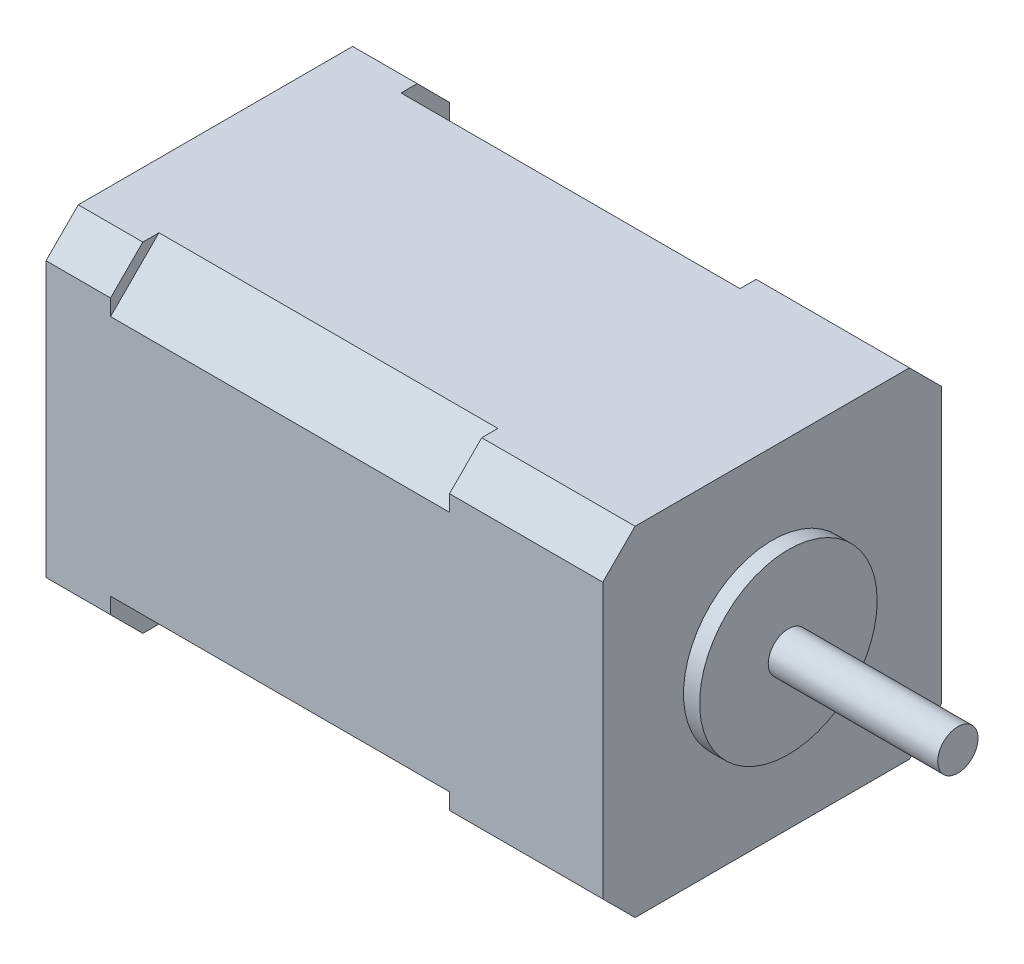
SolidWorks part; units mm, degrees
ref_plane "前视基准面" through (0, 0, 0) normal (0, 0, 1) x (1, 0, 0)
ref_plane "上视基准面" through (0, 0, 0) normal (0, 1, 0) x (1, 0, 0)
ref_plane "右视基准面" through (0, 0, 0) normal (1, 0, 0) x (0, 0, -1)
other "Configuration Table"
sketch "草图1" plane through (0, 0, 0) normal (1, 0, 0) x (0, 0, -1)
  line L1 (-21, 21) -> (21, 21)
  line L2 (-21, 21) -> (-21, -21)
  line L3 (-21, -21) -> (21, -21)
  line L4 (21, 21) -> (21, -21)
  dimension "D1" = 42
  dimension "D2" = 42
  dimension "D3" = 21
  dimension "D4" = 21
extrude "凸台-拉伸1" add sketch "草图1" along normal blind 69
sketch "草图2" plane through (69, 0, 0) normal (1, 0, 0) x (0, 0, -1)
  circle A0 centre (0, 0) radius 11
  dimension "D1" = 22
extrude "凸台-拉伸2" add sketch "草图2" along normal blind 2
sketch "草图3" plane through (71, 0, 0) normal (1, 0, 0) x (0, 0, -1)
  circle A0 centre (0, 0) radius 2.5
  dimension "D1" = 5
extrude "凸台-拉伸3" add sketch "草图3" along normal blind 21
sketch "草图5" plane through (0, 0, 0) normal (-1, 0, 0) x (0, 0, 1)
  line L0 (21, 15) -> (15, 21)
  line L1 (21, 21) -> (21, -21) construction
  line L2 (-21, 21) -> (21, 21) construction
  line L3 (15, 21) -> (21, 21)
  line L4 (21, 21) -> (21, 15)
  line L5 (-0.2819, 0) -> (49999.7181, 0) construction
  line L6 (0, 0) -> (0, -50000) construction
  line L7 (21, -21) -> (21, -15)
  line L8 (15, -21) -> (21, -21)
  line L9 (21, -15) -> (15, -21)
  line L10 (-21, 21) -> (-21, 15)
  line L11 (-15, 21) -> (-21, 21)
  line L12 (-21, 15) -> (-15, 21)
  line L13 (-21, -15) -> (-15, -21)
  line L14 (-15, -21) -> (-21, -21)
  line L15 (-21, -21) -> (-21, -15)
  dimension "D1" = 6
  dimension "D2" = 6
extrude "切除-拉伸1" cut sketch "草图5" against normal blind 42 from offset 8 offset against normal yes
chamfer "倒角1" distance 4 angle 45 8 edges at (4, -21, -21) (59.5, -21, -21) (59.5, -21, 21) (4, -21, 21) (4, 21, 21) (4, 21, -21) (59.5, 21, -21) (59.5, 21, 21)
